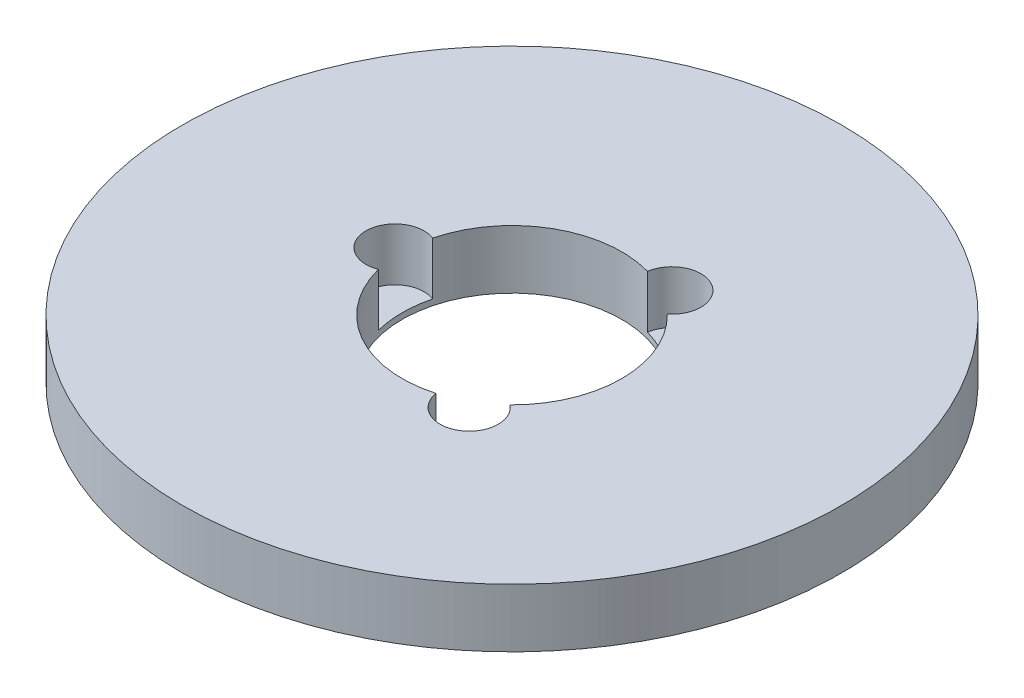
SolidWorks part; units mm, degrees
ref_plane "Front Plane" through (0, 0, 0) normal (0, 0, 1) x (1, 0, 0)
ref_plane "Top Plane" through (0, 0, 0) normal (0, 1, 0) x (1, 0, 0)
ref_plane "Right Plane" through (0, 0, 0) normal (1, 0, 0) x (0, 0, -1)
sketch "Sketch1" plane through (0, 0, 0) normal (0, 1, 0) x (1, 0, 0)
  circle A0 centre (0, 0) radius 90
  dimension "FLANGE_OD" = 180
extrude "Boss-Extrude1" add sketch "Sketch1" along normal blind 16
sketch "Sketch2" plane through (0, 0, 0) normal (0, 1, 0) x (1, 0, 0)
  circle A0 centre (0, 0) radius 30
  dimension "BORE_D" = 60
extrude "Cut-Extrude1" cut sketch "Sketch2" along normal through all
sketch "Sketch3" plane through (0, 16, 0) normal (0, 1, 0) x (1, 0, 0)
  circle A0 centre (0, 0) radius 31.9561 construction
  circle A1 centre (-31.9561, 0) radius 7.9403
  dimension "BOLT_D" = 15.8805
  dimension "BOLT_PCD" = 63.9122
extrude "Cut-Extrude2" cut sketch "Sketch3" against normal blind 14.3998
pattern_circular "CirPattern1" count 3 over 360 about axis through (0, 0, 0) along (0, 1, 0) of "Cut-Extrude2"
